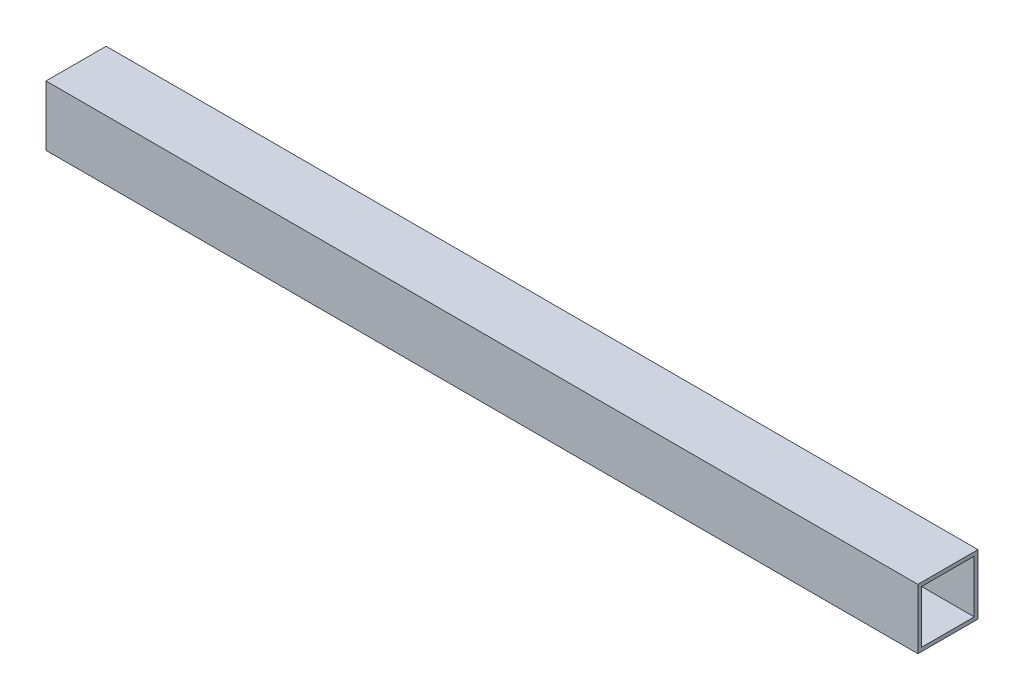
SolidWorks part; units mm, degrees
material "6061-T6 (SS)"
ref_plane "Front" through (0, 0, 0) normal (0, 0, 1) x (1, 0, 0)
ref_plane "Top" through (0, 0, 0) normal (0, 1, 0) x (1, 0, 0)
ref_plane "Right" through (0, 0, 0) normal (1, 0, 0) x (0, 0, -1)
sketch "Sketch1" plane through (0, 0, 0) normal (1, 0, 0) x (0, 0, -1)
  line L1 (-12.7, -12.7) -> (12.7, -12.7)
  line L2 (-12.7, -12.7) -> (-12.7, 12.7)
  line L3 (-12.7, 12.7) -> (12.7, 12.7)
  line L4 (12.7, -12.7) -> (12.7, 12.7)
  line L5 (-12.7, -12.7) -> (12.7, 12.7) construction
  line L6 (-12.7, 12.7) -> (12.7, -12.7) construction
  point P0 (0, 0)
  dimension "D1" = 25.4
extrude "Extrude-Thin1" add sketch "Sketch1" along normal up to surface (368.3 mm away) thin thin type one direction reverse wall 1.5875
